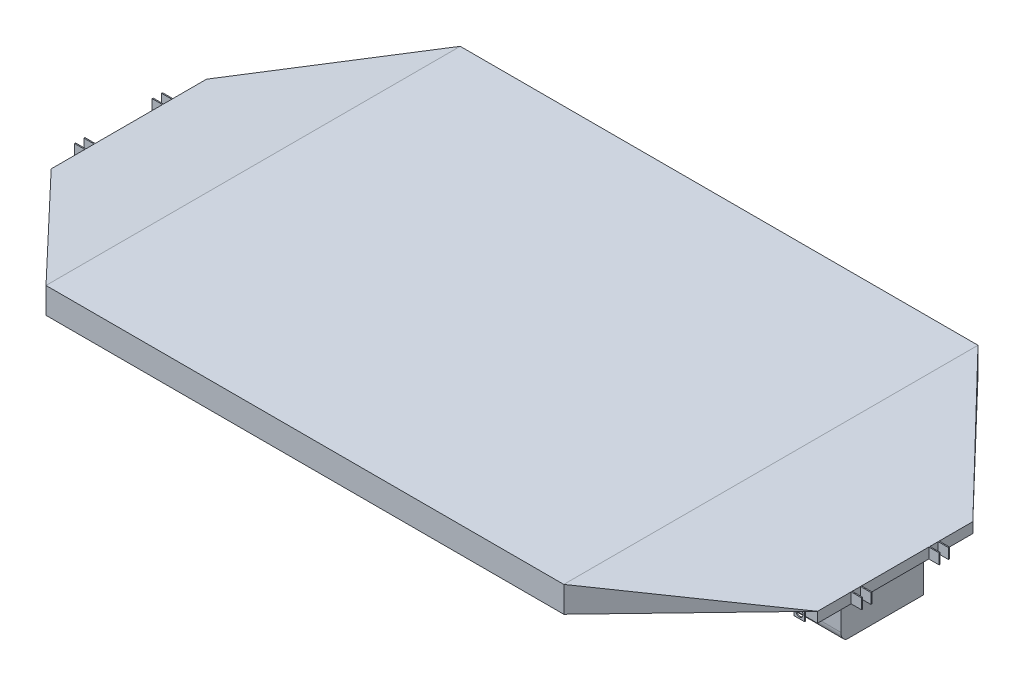
SolidWorks part; units mm, degrees
material "1060 Alloy"
ref_plane "Front Plane" through (0, 0, 0) normal (0, 0, 1) x (1, 0, 0)
ref_plane "Top Plane" through (0, 0, 0) normal (0, 1, 0) x (1, 0, 0)
ref_plane "Right Plane" through (0, 0, 0) normal (1, 0, 0) x (0, 0, -1)
sketch "Sketch1" plane through (0, 0, 0) normal (0, 1, 0) x (1, 0, 0)
  line L1 (3.5148, 13.895) -> (67.0148, 13.895)
  line L2 (3.5148, 13.895) -> (3.5148, -36.905)
  line L3 (3.5148, -36.905) -> (67.0148, -36.905)
  line L4 (67.0148, 13.895) -> (67.0148, -36.905)
  dimension "D1" = 63.5
  dimension "D2" = 50.8
extrude "Boss-Extrude1" add sketch "Sketch1" along normal blind 6.35
sketch "Sketch2" plane through (0, 0, 0) normal (0, 1, 0) x (1, 0, 0)
  line L0 (3.5148, 13.895) -> (3.5148, -36.905)
  line L1 (3.5148, -36.905) -> (-26.9652, -36.905)
  line L4 (-26.9652, -36.905) -> (-26.9652, -17.855)
  line L5 (-26.9652, -17.855) -> (3.5148, 13.895)
  dimension "D1" = 30.48
  dimension "D2" = 19.05
extrude "Boss-Extrude5" add sketch "Sketch2" along normal blind 6.35
sketch "Sketch7" plane through (0, 0, -13.895) normal (0, 0, -1) x (-1, 0, 0)
  line L0 (-3.5148, 6.35) -> (26.9652, 0)
  line L1 (26.9652, 0) -> (26.9652, 6.35)
  line L2 (26.9652, 6.35) -> (-3.5148, 6.35)
extrude "Cut-Extrude3" cut sketch "Sketch7" against normal blind 55.118
sketch "Sketch8" plane through (0, 0, 0) normal (0, -1, 0) x (-1, 0, 0)
  line L0 (26.9652, -17.855) -> (1.5652, -17.855)
  line L1 (1.5652, -17.855) -> (1.5652, -36.905)
  line L2 (26.9652, -36.905) -> (-67.0148, -36.905) construction
  line L3 (26.9652, -17.855) -> (26.9652, -36.905)
  line L4 (26.9652, -36.905) -> (1.5652, -36.905)
  dimension "D1" = 25.4
extrude "Boss-Extrude6" add sketch "Sketch8" along normal blind 2.54
sketch "Sketch11" plane through (0, -2.54, 0) normal (0, -1, 0) x (1, 0, 0)
  line L1 (-26.9652, 36.905) -> (-26.9652, 17.855) construction
  line L2 (-26.9652, 27.38) -> (-26.9652, 28.65)
  line L3 (-26.9652, 27.38) -> (-26.9652, 26.11)
  line L4 (-26.9652, 28.65) -> (-29.5052, 28.65)
  line L5 (-29.5052, 28.65) -> (-29.5052, 26.11)
  line L6 (-29.5052, 26.11) -> (-26.9652, 26.11)
  dimension "D1" = 1.27
  dimension "D2" = 1.27
  dimension "D3" = 2.54
extrude "Boss-Extrude9" add sketch "Sketch11" against normal blind 2.54
sketch "Sketch13" plane through (-29.5052, 0, 0) normal (-1, 0, 0) x (0, 0, 1)
  line L0 (27.38, 0) -> (26.364, 0)
  line L1 (26.11, 0) -> (28.65, 0) construction
  line L2 (27.38, 0) -> (28.396, 0)
  line L3 (26.364, 0) -> (26.364, -2.54)
  line L4 (28.65, -2.54) -> (26.11, -2.54) construction
  line L5 (26.364, -2.54) -> (27.38, -2.54)
  line L6 (27.38, -2.54) -> (28.396, -2.54)
  line L7 (28.396, -2.54) -> (28.396, 0)
  dimension "D1" = 1.016
  dimension "D2" = 1.016
extrude "Cut-Extrude5" cut sketch "Sketch13" against normal blind 2.54
sketch "Sketch14" plane through (0, -2.54, 0) normal (0, -1, 0) x (1, 0, 0)
  line L0 (-14.2652, 36.905) -> (-7.9152, 36.905)
  line L1 (-1.5652, 36.905) -> (-26.9652, 36.905) construction
  line L2 (-14.2652, 36.905) -> (-20.6152, 36.905)
  line L3 (-20.6152, 36.905) -> (-20.6152, 26.745)
  line L4 (-20.6152, 26.745) -> (-7.9152, 26.745)
  line L5 (-7.9152, 26.745) -> (-7.9152, 36.905)
  dimension "D1" = 6.35
  dimension "D2" = 6.35
  dimension "D3" = 10.16
extrude "Boss-Extrude10" add sketch "Sketch14" along normal blind 10.16
sketch "Sketch15" plane through (-20.6152, 0, 0) normal (-1, 0, 0) x (0, 0, 1)
  line L1 (36.905, -12.7) -> (26.745, -12.7) construction
  line L4 (28.015, -12.7) -> (28.015, -11.43)
  line L6 (36.905, -12.7) -> (36.905, -2.54) construction
  line L7 (28.015, -11.43) -> (36.905, -6.35)
  line L8 (28.015, -12.7) -> (36.905, -12.7)
  line L9 (36.905, -12.7) -> (36.905, -6.35)
  dimension "D3" = 1.27
extrude "Cut-Extrude6" cut sketch "Sketch15" against normal blind 12.7
sketch "Sketch16" plane through (0, 0, 17.855) normal (0, 0, -1) x (-1, 0, 0)
  line L0 (22.5202, -2.54) -> (22.5202, 0)
  line L1 (23.7902, -2.54) -> (22.5202, -2.54)
  line L2 (23.7902, -2.54) -> (25.0602, -2.54)
  line L3 (-3.5148, 0) -> (26.9652, 0) construction
  line L4 (22.5202, 0) -> (25.0602, 0)
  line L5 (25.0602, 0) -> (25.0602, -2.54)
  dimension "D1" = 1.27
  dimension "D2" = 1.27
extrude "Boss-Extrude11" add sketch "Sketch16" along normal blind 1.27
extrude "Cut-Extrude7" cut sketch "Sketch16<2>" along normal blind 1.016
sketch "Sketch16<2>" plane through (0, 0, 17.855) normal (0, 0, -1) x (-1, 0, 0) same geometry as "Sketch16"
sketch "Sketch18" plane through (0, 0, 17.855) normal (0, 0, -1) x (-1, 0, 0)
  line L2 (4.7402, -2.54) -> (3.4702, -2.54)
  line L3 (4.7402, -2.54) -> (6.0102, -2.54)
  line L4 (3.4702, -2.54) -> (3.4702, 0)
  line L5 (26.9652, 0) -> (1.5652, 0) construction
  line L6 (3.4702, 0) -> (6.0102, 0)
  line L7 (6.0102, 0) -> (6.0102, -2.54)
  dimension "D2" = 1.27
  dimension "D3" = 1.27
extrude "Boss-Extrude12" add sketch "Sketch18" along normal blind 15.494
extrude "Cut-Extrude8" cut sketch "Sketch18<2>" along normal blind 15.24
sketch "Sketch18<2>" plane through (0, 0, 17.855) normal (0, 0, -1) x (-1, 0, 0) same geometry as "Sketch18"
extrude "Boss-Extrude14" add sketch "Sketch18<4>" along normal blind 7.874
sketch "Sketch18<4>" plane through (0, 0, 17.855) normal (0, 0, -1) x (-1, 0, 0) same geometry as "Sketch18"
extrude "Cut-Extrude9" cut sketch "Sketch18<5>" along normal blind 7.62
sketch "Sketch18<5>" plane through (0, 0, 17.855) normal (0, 0, -1) x (-1, 0, 0) same geometry as "Sketch18"
sketch "Sketch19" plane through (0, 0, 2.361) normal (0, 0, -1) x (-1, 0, 0)
  circle A2 centre (4.7402, -1.27) radius 0.889
sketch "Sketch20" plane through (0, 0, 16.585) normal (0, 0, -1) x (-1, 0, 0)
  circle A0 centre (23.7902, -1.27) radius 0.889
extrude "Cut-Extrude12" cut sketch "Sketch20" against normal blind 0.762
extrude "Cut-Extrude13" cut sketch "Sketch19" against normal blind 11.938
sketch "Sketch21" plane through (0, -2.54, 0) normal (0, -1, 0) x (1, 0, 0)
  line L0 (-20.6152, 36.905) -> (-26.9652, 36.905) construction
  line L1 (-23.7902, 36.905) -> (-20.6152, 36.905)
  line L2 (-23.7902, 36.905) -> (-23.7902, 26.745)
  line L3 (-23.7902, 26.745) -> (-20.6152, 26.745)
  line L4 (-20.6152, 36.905) -> (-20.6152, 26.745)
  line L5 (-1.5652, 36.905) -> (-7.9152, 36.905) construction
  line L6 (-7.9152, 26.745) -> (-4.7402, 26.745)
  line L7 (-7.9152, 26.745) -> (-7.9152, 36.905)
  line L8 (-7.9152, 36.905) -> (-4.7402, 36.905)
  line L9 (-4.7402, 26.745) -> (-4.7402, 36.905)
extrude "Boss-Extrude15" add sketch "Sketch21" along normal blind 10.16
sketch "Sketch22" plane through (0, 0, 36.905) normal (0, 0, 1) x (1, 0, 0)
  line L0 (-23.7902, -12.7) -> (-20.6152, -6.35)
  line L1 (-20.6152, -6.35) -> (-20.6152, -12.7)
  line L2 (-20.6152, -12.7) -> (-23.7902, -12.7)
  line L3 (-7.9152, -6.35) -> (-4.7402, -12.7)
  line L4 (-4.7402, -12.7) -> (-7.9152, -12.7)
  line L5 (-7.9152, -12.7) -> (-7.9152, -6.35)
extrude "Cut-Extrude15" cut sketch "Sketch22" against normal blind 10.16
sketch "Sketch23" plane through (-20.6152, 0, 0) normal (-1, 0, 0) x (0, 0, 1)
  line L0 (28.015, -12.7) -> (26.745, -12.7)
  line L1 (26.745, -12.7) -> (26.745, -6.35)
  line L2 (26.745, -6.35) -> (36.905, -6.35)
  line L3 (36.905, -6.35) -> (28.015, -11.43)
  line L4 (28.015, -11.43) -> (28.015, -12.7)
extrude "Boss-Extrude16" add sketch "Sketch23" along normal blind 3.175
extrude "Boss-Extrude17" add sketch "Sketch23<2>" against normal blind 15.875
sketch "Sketch23<2>" plane through (-20.6152, 0, 0) normal (-1, 0, 0) x (0, 0, 1) same geometry as "Sketch23"
sketch "Sketch24" plane through (0, 0, 0) normal (0, -1, 0) x (1, 0, 0)
  circle A0 centre (-2.2002, 6.298) radius 1.27
  dimension "D4" = 2.54
extrude "Cut-Extrude16" cut sketch "Sketch24" against normal blind 3.81
mirror "Mirror1" about plane through (3.5148, 6.35, 36.905) normal (0, 0, -1) of "Cut-Extrude16", "Boss-Extrude17", "Boss-Extrude16", "Cut-Extrude15", "Boss-Extrude15", "Cut-Extrude13", "Cut-Extrude12", "Cut-Extrude9", "Boss-Extrude14", "Cut-Extrude8", "Boss-Extrude12", "Cut-Extrude7", "Boss-Extrude11", "Cut-Extrude6", "Boss-Extrude10", "Cut-Extrude5", "Boss-Extrude9", "Boss-Extrude6", "Cut-Extrude3", "Boss-Extrude5", "Boss-Extrude1"
mirror "Mirror3" about plane through (67.0148, 6.35, -13.895) normal (-1, 0, 0) of "Mirror1", "Cut-Extrude16", "Boss-Extrude17", "Boss-Extrude16", "Cut-Extrude15", "Boss-Extrude15", "Cut-Extrude13", "Cut-Extrude12", "Cut-Extrude9", "Boss-Extrude14", "Cut-Extrude8", "Boss-Extrude12", "Cut-Extrude7", "Boss-Extrude11", "Cut-Extrude6", "Boss-Extrude10", "Cut-Extrude5", "Boss-Extrude9", "Boss-Extrude6", "Cut-Extrude3", "Boss-Extrude5", "Boss-Extrude1"
fillet "Fillet2" radius 1.27 1 edges at (-14.2652, -12.7, 45.795)
fillet "Fillet3" radius 2.54 1 edges at (-14.2652, -12.7, 26.745)
fillet "Fillet4" radius 2.54 1 edges at (148.2948, -12.7, 47.065)
fillet "Fillet5" radius 1.27 1 edges at (148.2948, -12.7, 28.015)
